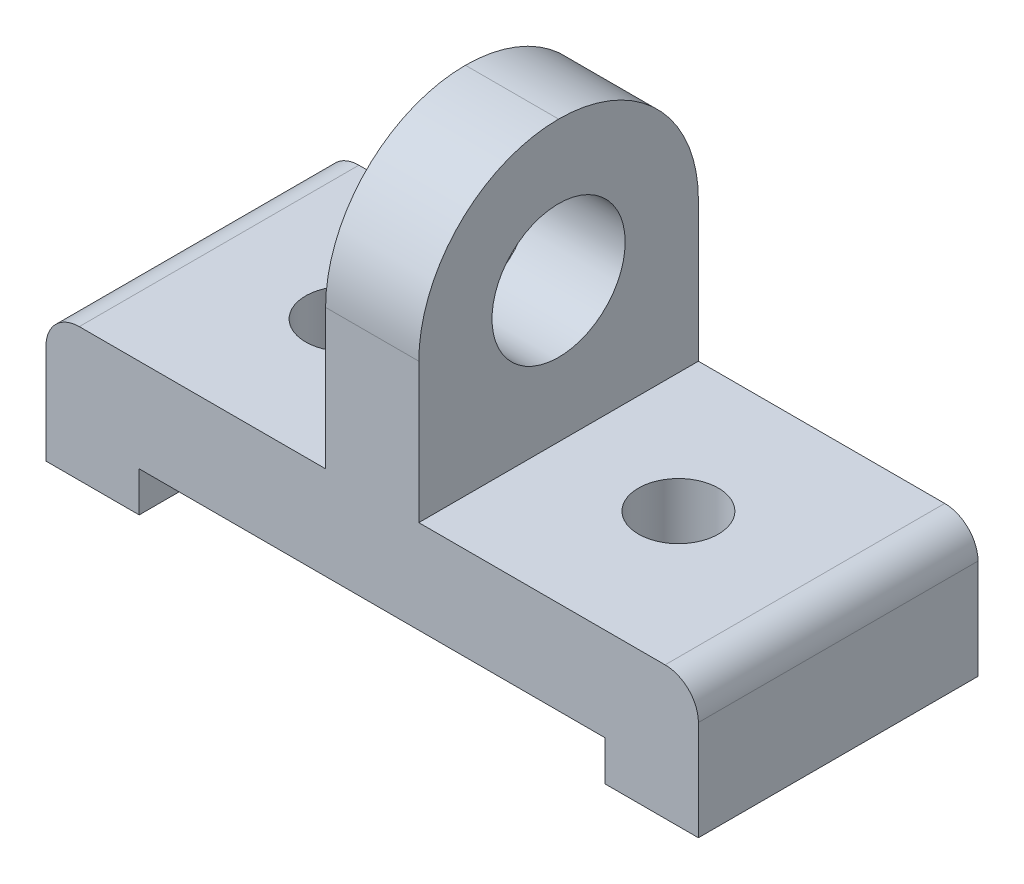
SolidWorks part; units mm, degrees
ref_plane "Front Plane" through (0, 0, 0) normal (0, 0, 1) x (1, 0, 0)
ref_plane "Top Plane" through (0, 0, 0) normal (0, 1, 0) x (1, 0, 0)
ref_plane "Right Plane" through (0, 0, 0) normal (1, 0, 0) x (0, 0, -1)
sketch "Sketch1" plane through (0, 0, 0) normal (0, 0, 1) x (1, 0, 0)
  line L0 (0, 0) -> (-14, 0)
  line L1 (-14, 0) -> (-14, 20)
  line L2 (-14, 20) -> (84, 20)
  line L3 (84, 20) -> (84, 0)
  line L4 (84, 0) -> (70, 0)
  line L5 (70, 0) -> (70, 6)
  line L6 (70, 6) -> (0, 6)
  line L7 (0, 6) -> (0, 0)
  dimension "D1" = 20
  dimension "D2" = 20
  dimension "D3" = 6
  dimension "D4" = 98
  dimension "D5" = 14
  dimension "D6" = 14
sketch "Sketch2" plane through (0, 0, 0) normal (0, 0, 1) x (1, 0, 0)
sketch "Sketch3" plane through (0, 0, 0) normal (0, 0, 1) x (1, 0, 0)
extrude "Boss-Extrude1" add sketch "Sketch1" against normal blind 42
sketch "Sketch4" plane through (0, 20, 0) normal (0, 1, 0) x (1, 0, 0)
  line L0 (-14, 21) -> (84, 21) construction
  line L1 (-14, 42) -> (-14, 0) construction
  line L2 (84, 42) -> (84, 0) construction
  line L4 (35, 42) -> (35, 0) construction
  line L5 (84, 42) -> (-14, 42) construction
  line L6 (84, 0) -> (-14, 0) construction
  circle A0 centre (60, 21) radius 6
  circle A1 centre (10, 21) radius 6
  dimension "D1" = 12
  dimension "D2" = 24
extrude "Cut-Extrude1" cut sketch "Sketch4" against normal blind 42
sketch "Sketch6" plane through (0, 20, 0) normal (0, 1, 0) x (1, 0, 0)
  line L0 (-14, 21) -> (84, 21) construction
  line L1 (-14, 42) -> (-14, 0) construction
  line L2 (84, 42) -> (84, 0) construction
  line L3 (35, 42) -> (35, 0) construction
  line L4 (84, 42) -> (-14, 42) construction
  line L5 (84, 0) -> (-14, 0) construction
  line L7 (28, 42) -> (42, 42)
  line L8 (28, 42) -> (28, 0)
  line L9 (28, 0) -> (42, 0)
  line L10 (42, 42) -> (42, 0)
  dimension "D1" = 14
  dimension "D2" = 7
extrude "Boss-Extrude2" add sketch "Sketch6" along normal blind 42
fillet "Fillet1" radius 21 2 edges at (35, 62, -42) (35, 62, 0)
sketch "Sketch7" plane through (42, 0, 0) normal (1, 0, 0) x (0, 0, -1)
  line L0 (21, 62) -> (21, 20) construction
  line L1 (0, 20) -> (42, 20) construction
  line L2 (0, 41) -> (42, 41) construction
  circle A0 centre (21, 41) radius 10
  dimension "D1" = 20
extrude "Cut-Extrude2" cut sketch "Sketch7" against normal blind 42
fillet "Fillet4" radius 5 2 edges at (-14, 20, -21) (84, 20, -21)
